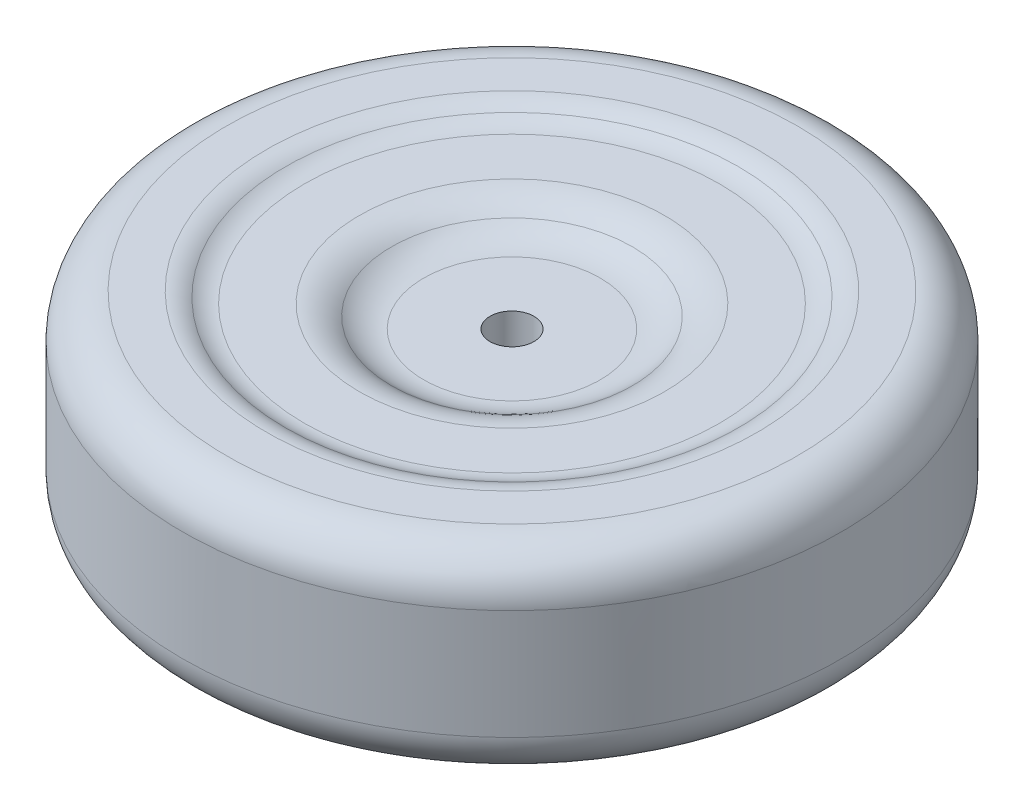
SolidWorks part; units mm, degrees
material "AISI 1020"
ref_plane "Front Plane" through (0, 0, 0) normal (0, 0, 1) x (1, 0, 0)
ref_plane "Top Plane" through (0, 0, 0) normal (0, 1, 0) x (1, 0, 0)
ref_plane "Right Plane" through (0, 0, 0) normal (1, 0, 0) x (0, 0, -1)
sketch "Sketch1" plane through (0, 0, 0) normal (0, 1, 0) x (1, 0, 0)
  circle A0 centre (0, 0) radius 190.5
  dimension "D1" = 381
extrude "Boss-Extrude1" add sketch "Sketch1" along normal blind 57.15
sketch "Sketch2" plane through (0, 57.15, 0) normal (0, 1, 0) x (1, 0, 0)
  circle A0 centre (0, 0) radius 127
  circle A1 centre (0, 0) radius 19.05
extrude "Cut-Extrude1" cut sketch "Sketch2" against normal blind 484.378 contours A1
sketch "Sketch3" plane through (0, 0, 0) normal (0, -1, 0) x (-1, 0, 0)
  circle A0 centre (0, 0) radius 127
extrude "Cut-Extrude2" cut sketch "Sketch3" against normal blind 6.35
sketch "Sketch4" plane through (0, 0, 0) normal (0, 1, 0) x (1, 0, 0)
  circle A0 centre (0, 0) radius 127
  circle A1 centre (0, 0) radius 63.5
extrude "Cut-Extrude3" cut sketch "Sketch4" along normal blind 19.05 contours A1
fillet "Fillet1" radius 20.32 1 edges at (0, 0, -127)
fillet "Fillet2" radius 20.32 1 edges at (0, 6.35, -127)
fillet "Fillet3" radius 30.48 1 edges at (0, 6.35, -63.5)
fillet "Fillet4" radius 30.48 1 edges at (0, 19.05, 63.5)
ref_plane "Plane1" through (0, 57.15, 0) normal (0, 1, 0) x (1, 0, 0)
mirror "Mirror2" about plane through (0, 57.15, 0) normal (0, 1, 0) of "Cut-Extrude1", "Cut-Extrude3", "Fillet4", "Fillet3", "Cut-Extrude2", "Fillet2", "Fillet1", "Boss-Extrude1"
fillet "Fillet7" radius 25.4 1 edges at (0, 114.3, 190.5)
fillet "Fillet8" radius 25.4 1 edges at (0, 0, 190.5)
split "Split2" bodies to split 106 resulting bodies 108
sketch "Sketch5" plane through (0, 95.25, 0) normal (0, 1, 0) x (1, 0, 0)
  circle A0 centre (0, 0) radius 51.0131
extrude "Boss-Extrude3" add sketch "Sketch5" against normal up to surface (76.2 mm away) up to face at (0, 19.05, 51.0131)
sketch "Sketch6" plane through (0, 95.25, 0) normal (0, 1, 0) x (1, 0, 0)
  circle A0 centre (0, 0) radius 12.7
extrude "Cut-Extrude4" cut sketch "Sketch6" against normal blind 1040.638
